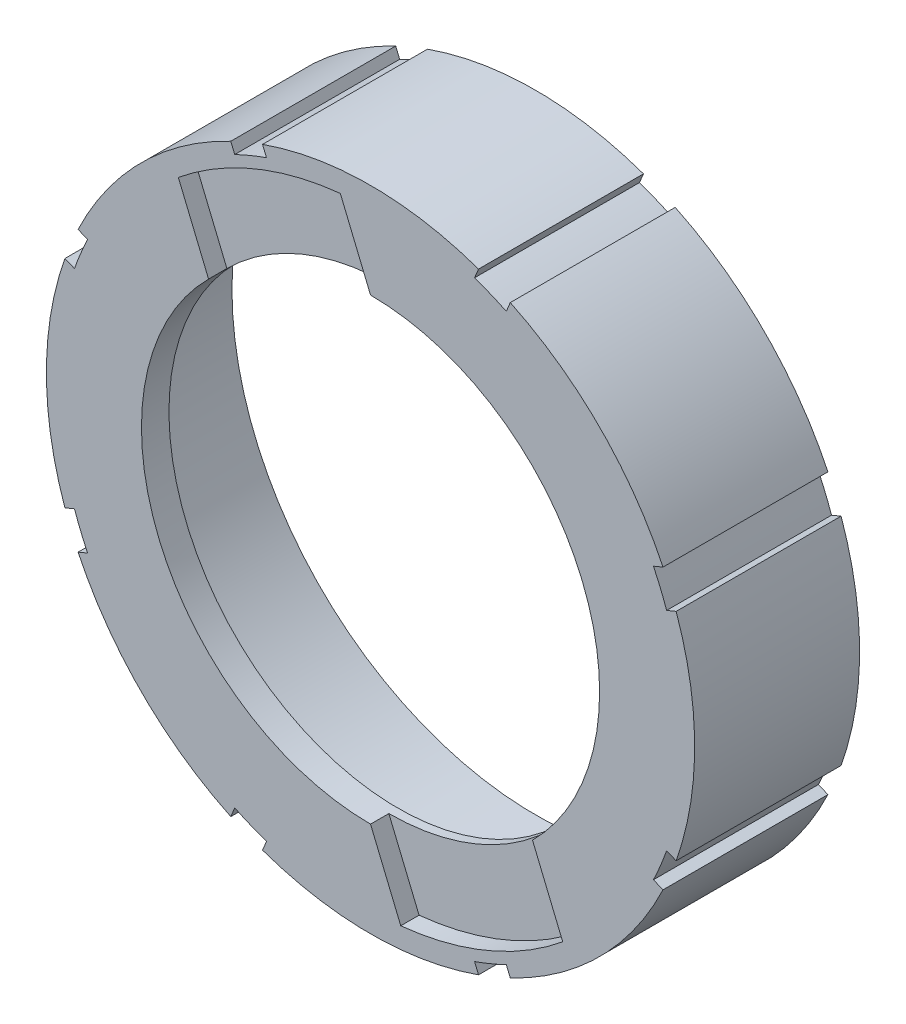
SolidWorks part; units mm, degrees
ref_plane "Front Plane" through (0, 0, 0) normal (0, 0, 1) x (1, 0, 0)
ref_plane "Top Plane" through (0, 0, 0) normal (0, 1, 0) x (1, 0, 0)
ref_plane "Right Plane" through (0, 0, 0) normal (1, 0, 0) x (0, 0, -1)
sketch "Sketch1" plane through (0, 0, 0) normal (0, 0, 1) x (1, 0, 0)
  circle A4 centre (0, 0) radius 14.15
  circle A6 centre (0, 0) radius 13.25
  dimension "D1" = 26.5
  dimension "D2" = 28.3
extrude "Boss-Extrude1" add sketch "Sketch1" against normal blind 6
sketch "Sketch2" plane through (0, 0, 0) normal (0, 0, 1) x (1, 0, 0)
  circle A1 centre (0, 0) radius 10
  circle A6 centre (0, 0) radius 14.15 construction
  circle A7 centre (0, 0) radius 14.15
  dimension "D1" = 20
extrude "Boss-Extrude2" add sketch "Sketch2" along normal blind 1.2
sketch "Sketch3" plane through (0, 0, 0) normal (0, 0, -1) x (-1, 0, 0)
  line L0 (0, 0) -> (0, -13.25)
  line L1 (0, 0) -> (-9.3912, -9.3471)
  line L2 (-0.0268, 0.1737) -> (0, 0) construction
  line L3 (0, 0) -> (-5.0706, -12.2414) construction
  line L4 (0, -10) -> (-1.3189, -13.1842)
  line L5 (-7.0711, -7.0711) -> (-8.39, -10.2553)
  circle A0 centre (0, 0) radius 10 construction
  circle A1 centre (0, 0) radius 13.25
  circle A2 centre (0, 0) radius 13.25
  circle A3 centre (0, 0) radius 10
  dimension "D2" = 22.5
  dimension "D1" = 0
sketch "Sketch4" plane through (0, 0, 1.2) normal (0, 0, 1) x (1, 0, 0)
  line L0 (8.39, -10.2553) -> (-1.6776, 14.0502)
  line L1 (0, -10) -> (-8.7487, 11.1213)
  line L3 (7.0711, -7.0711) -> (8.39, -10.2553) construction
  line L4 (0, -10) -> (1.3189, -13.1842) construction
  line L5 (7.0711, -7.0711) -> (8.39, -10.2553)
  line L6 (0, -10) -> (1.3189, -13.1842)
  line L7 (0, 0) -> (3.5355, 1.4645) construction
  circle A0 centre (0, 0) radius 14.15 construction
  arc A2 (-1.6776, 14.0502) -> (-8.7487, 11.1213) centre (0, 0) ccw
  circle A3 centre (0, 0) radius 13.25 construction
  circle A4 centre (0, 0) radius 13.25 construction
  arc A5 (1.3189, -13.1842) -> (8.39, -10.2553) centre (0, 0) ccw
  arc A6 (1.3189, -13.1842) -> (8.39, -10.2553) centre (0, 0) ccw
  arc A7 (-1.3189, 13.1842) -> (-8.39, 10.2553) centre (0, 0) ccw
  arc A8 (-1.3189, 13.1842) -> (-8.39, 10.2553) centre (0, 0) ccw
  circle M8 centre (0, 0) radius 10
extrude "Cut-Extrude2" cut sketch "Sketch4" against normal blind 0.8 contours L0 A5 L1 M8 | L6 A5 L0 M8 region at (4.3639, -10.5354, 1.2) region at (-4.3639, 10.5354, 1.2)
sketch "Sketch5" plane through (0, 0, -6) normal (0, 0, -1) x (-1, 0, 0)
  line L0 (4.7144, 13.3415) -> (-0.6908, 0.2921)
  line L1 (6.1003, 12.7675) -> (0.6886, -0.2975)
  line L2 (0, 0) -> (3.8268, 9.2388) construction
  arc A0 (7.0711, 7.0711) -> (0, 10) centre (0, 0) ccw construction
  circle A1 centre (0, 0) radius 14.15
  circle A2 centre (0, 0) radius 14.15
  arc A3 (7.0711, 7.0711) -> (0, 10) centre (0, 0) ccw
  circle A4 centre (0, 0) radius 13.7
  point P10 (3.8268, 9.2388)
  circle M6 centre (0, 0) radius 14.15
  dimension "D4" = 27.4
  dimension "D2" = 1.5
  dimension "D3" = 0.75
  dimension "D1" = 0
extrude "Cut-Extrude3" cut sketch "Sketch5" against normal through all contours A4 L1 L0 M6 region at (-5.3263, 12.8588, -6)
ref_axis "Axis1" through (0, 0, 0) along (0, 0, 1)
pattern_circular "CirPattern1" count 8 over 360 about axis through (0, 0, 0) along (0, 0, 1) of "Cut-Extrude3"
